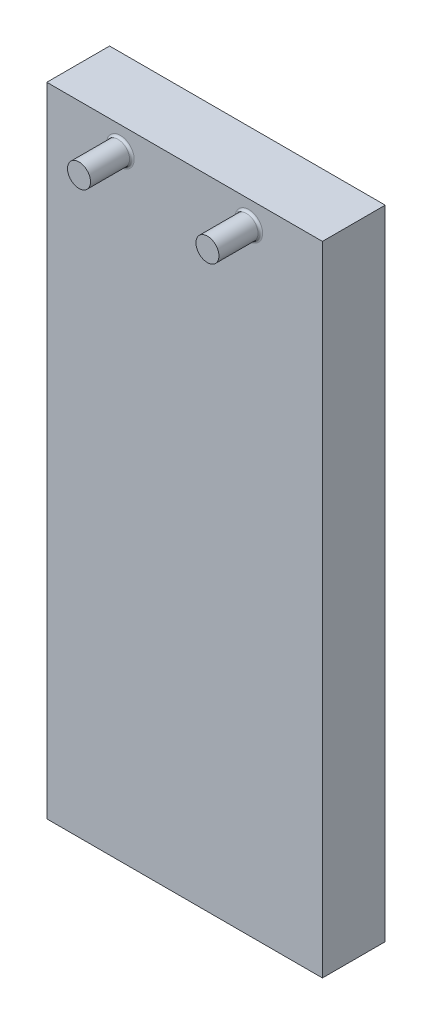
SolidWorks part; units mm, degrees
ref_plane "Front Plane" through (0, 0, 0) normal (0, 0, 1) x (1, 0, 0)
ref_plane "Top Plane" through (0, 0, 0) normal (0, 1, 0) x (1, 0, 0)
ref_plane "Right Plane" through (0, 0, 0) normal (1, 0, 0) x (0, 0, -1)
sketch "Sketch1" plane through (0, 0, 0) normal (0, 1, 0) x (1, 0, 0)
  line L1 (-59.92, -13.65) -> (59.92, -13.65)
  line L2 (-59.92, -13.65) -> (-59.92, 13.65)
  line L3 (-59.92, 13.65) -> (59.92, 13.65)
  line L4 (59.92, -13.65) -> (59.92, 13.65)
  line L5 (-59.92, -13.65) -> (59.92, 13.65) construction
  line L6 (-59.92, 13.65) -> (59.92, -13.65) construction
  point P0 (0, 0)
  dimension "D1" = 119.84
  dimension "D2" = 27.3
extrude "Boss-Extrude1" add sketch "Sketch1" along normal blind 277.37
sketch "Sketch2" plane through (0, 0, 13.65) normal (0, 0, 1) x (1, 0, 0)
  line L0 (-59.92, 257.37) -> (59.92, 257.37)
  line L1 (-59.92, 277.37) -> (-59.92, 0) construction
  line L2 (59.92, 277.37) -> (59.92, 0) construction
  line L3 (-59.92, 277.37) -> (59.92, 277.37) construction
  line L4 (-59.92, 257.37) -> (-59.92, 277.37)
  line L5 (-59.92, 267.37) -> (59.92, 267.37) construction
  circle A2 centre (-27.92, 267.37) radius 5
  circle A3 centre (27.92, 267.37) radius 5
  dimension "D4" = 10
  dimension "D1" = 20
  dimension "D2" = 32
  dimension "D3" = 32
extrude "Boss-Extrude2" add sketch "Sketch2" along normal blind 18 contours L5 A3 | A3 L5 | L5 A2 | A2 L5 region at (-27.92, 269.4921, 13.65) region at (27.92, 269.4921, 13.65) region at (27.92, 265.2479, 13.65) region at (-27.92, 265.2479, 13.65)
fillet "Fillet1" radius 1 2 edges at (22.92, 267.37, 13.65) (-32.92, 267.37, 13.65)
equation "\"PCWidth\"= 340mm'Distance of longest part parallel to GPU(ussually GPU)"
equation "\"PCLength\"= 145mm'Length across I/O from PS to GPU"
equation "\"PCHeight\"= 180mm'Tallest point with mobo laying flat"
equation "\"WallThickness\"= 9mm'Thickness of each outer tank wall"
equation "\"ThermoBarrierThickness\"= 6mm'Thickness of barrier between hot side and cold side"
equation "\"HotSideGap\"= 36mm'Space in the hot side for a pump"
equation "\"PCClearance\"= 40mm'Clearance from top of tank to top of PC"
equation "\"RadiatorHeight\"= 277.37mm'Final Height from ground of radiators"
equation "\"D1@Boss-Extrude1\"=\"RadiatorHeight\""
